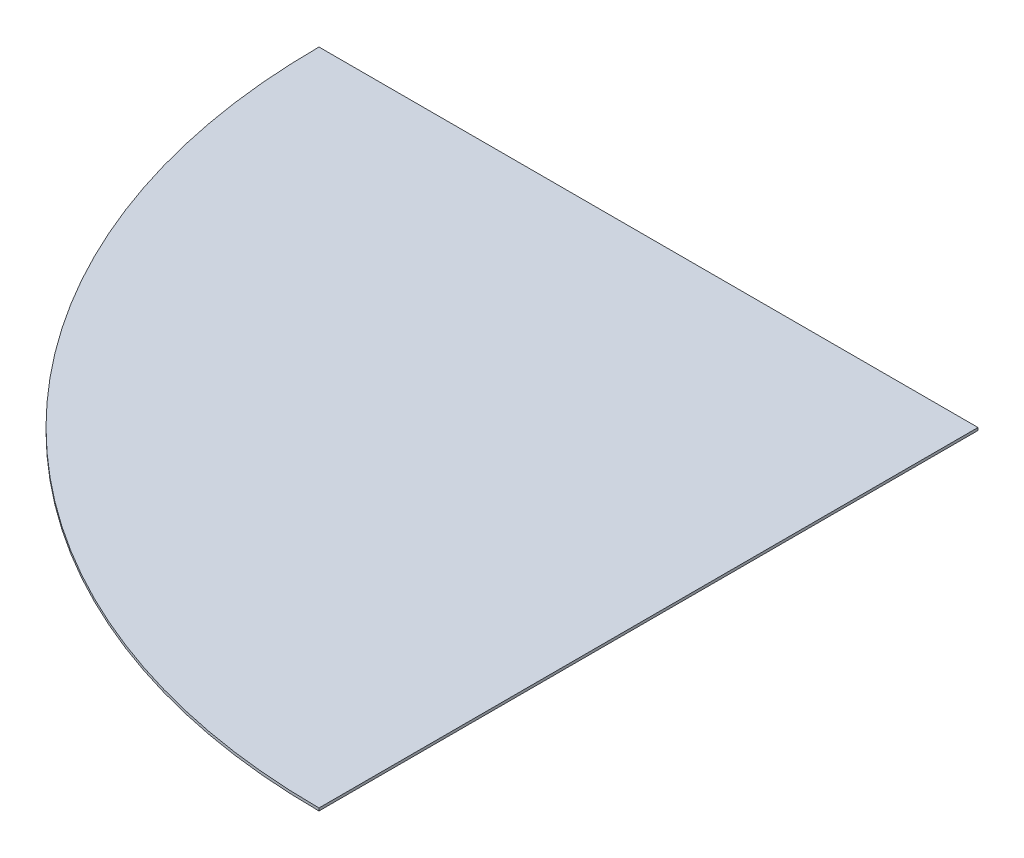
SolidWorks part; units mm, degrees
material "普通碳钢"
ref_plane "前视基准面" through (0, 0, 0) normal (0, 0, 1) x (1, 0, 0)
ref_plane "上视基准面" through (0, 0, 0) normal (0, 1, 0) x (1, 0, 0)
ref_plane "右视基准面" through (0, 0, 0) normal (1, 0, 0) x (0, 0, -1)
sketch "草图1" plane through (0, 0, 0) normal (0, 1, 0) x (1, 0, 0)
  line L0 (-92.5, 0) -> (92.5, 0) construction
  line L1 (0, -92.5) -> (0, 92.5) construction
  line L2 (-92.5, 0) -> (-92.5, -92.5) construction
  line L3 (-92.5, -92.5) -> (0, -92.5) construction
  line L4 (-92.5, -92.5) -> (-592.5, -92.5) construction
  line L5 (-92.5, -92.5) -> (-92.5, -592.5) construction
  line L6 (-592.5, -92.5) -> (-92.5, -92.5)
  line L7 (-92.5, -92.5) -> (-92.5, -592.5)
  circle A0 centre (-92.5, -92.5) radius 500 construction
  arc A1 (-592.5, -92.5) -> (-92.5, -592.5) centre (-92.5, -92.5) ccw
  dimension "D5" = 500
  dimension "D3" = 1000
  dimension "D1" = 185
  dimension "D2" = 185
  dimension "D4" = 500
base flange "基体-法兰1" sketch "草图1" thickness 2 reverse thickness direction yes parameters "D1"=1
sketch "折弯-线1" plane through (0, 0, 0) normal (0, 1, 0) x (1, 0, 0)
sketch "边界框1" plane through (0, 0, 0) normal (0, 1, 0) x (1, 0, 0)
sheet metal parameters "钣金1" thickness 2 parameters "D1"=1
flat pattern "平板型式1" [suppressed]
sketch "折弯-线2" plane through (0, 0, 0) normal (0, 1, 0) x (1, 0, 0)
sketch "边界框2" [suppressed] plane through (0, 0, 0) normal (0, 1, 0) x (1, 0, 0)
